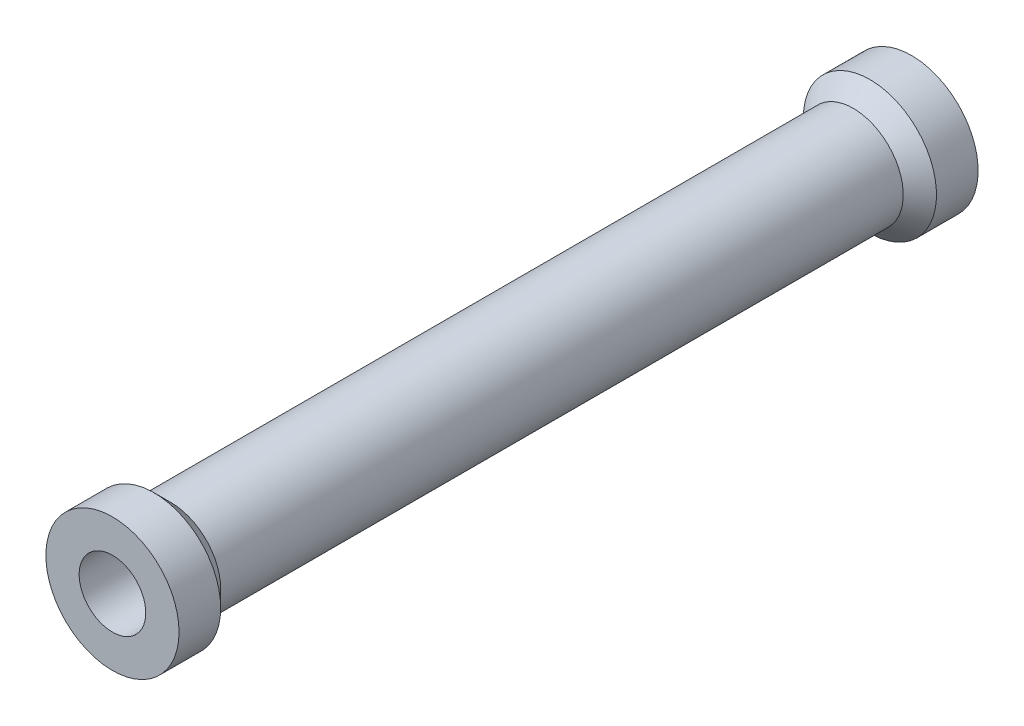
SolidWorks part; units mm, degrees
ref_plane "Front Plane" through (0, 0, 0) normal (0, 0, 1) x (1, 0, 0)
ref_plane "Top Plane" through (0, 0, 0) normal (0, 1, 0) x (1, 0, 0)
ref_plane "Right Plane" through (0, 0, 0) normal (1, 0, 0) x (0, 0, -1)
sketch "Sketch1" plane through (0, 0, 0) normal (0, 0, 1) x (1, 0, 0)
  circle A0 centre (0, 0) radius 4.7625
  dimension "D1" = 9.525
extrude "Boss-Extrude1" add sketch "Sketch1" along normal blind 31.75
sketch "Sketch2" plane through (0, 0, 31.75) normal (0, 0, 1) x (1, 0, 0)
  circle A0 centre (0, 0) radius 6.35
extrude "Boss-Extrude2" add sketch "Sketch2" along normal blind 6.35
chamfer "Chamfer1" distance 2.38 angle 45 1 edges at (6.35, 0, 31.75)
sketch "Sketch3" plane through (0, 0, 38.1) normal (0, 0, 1) x (1, 0, 0)
  circle A0 centre (0, 0) radius 3.175
extrude "Cut-Extrude1" cut sketch "Sketch3" against normal blind 12.7
sketch "Sketch4" plane through (0, 0, 0) normal (0, 0, -1) x (-1, 0, 0)
  circle A0 centre (0, 0) radius 4.7625
extrude "Boss-Extrude3" add sketch "Sketch4" along normal blind 31.75
sketch "Sketch5" plane through (0, 0, -31.75) normal (0, 0, -1) x (-1, 0, 0)
  circle A0 centre (0, 0) radius 6.35
extrude "Boss-Extrude4" add sketch "Sketch5" along normal blind 6.35
chamfer "Chamfer2" distance 2.38 angle 45 1 edges at (-6.35, 0, -31.75)
sketch "Sketch6" plane through (0, 0, -38.1) normal (0, 0, -1) x (-1, 0, 0)
  circle A0 centre (0, 0) radius 3.175
extrude "Cut-Extrude2" cut sketch "Sketch6" against normal blind 12.7
sketch "Sketch7" plane through (0, 0, -38.1) normal (0, 0, -1) x (-1, 0, 0)
  point P0 (0, 0)
